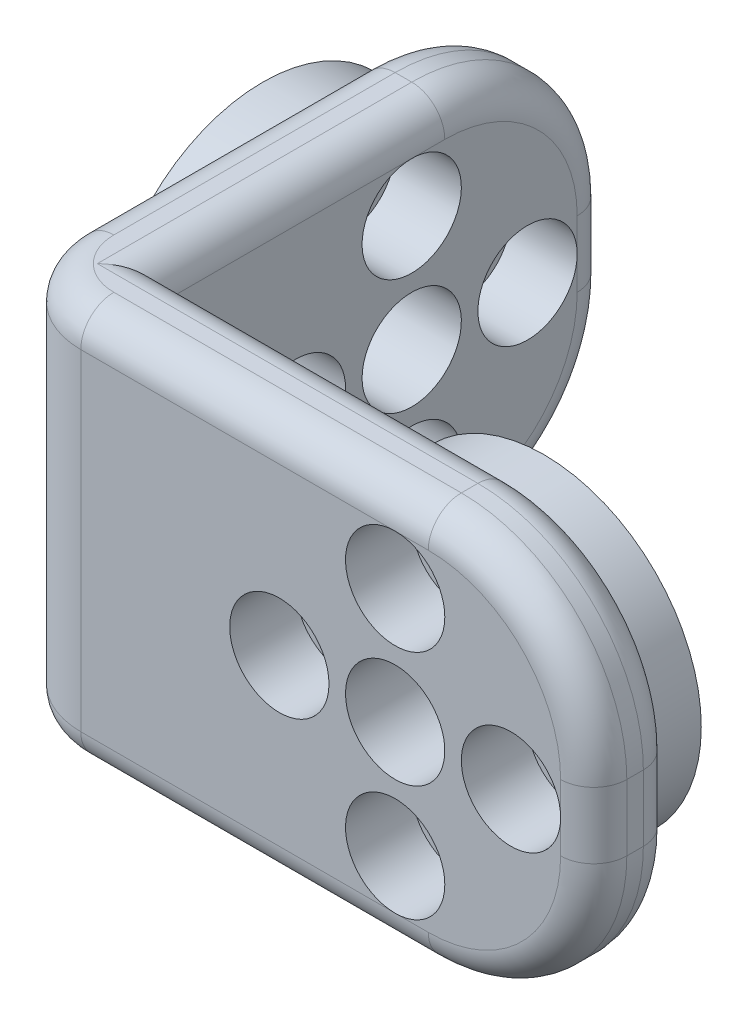
SolidWorks part; units mm, degrees
ref_plane "前视基准面" through (0, 0, 0) normal (0, 0, 1) x (1, 0, 0)
ref_plane "上视基准面" through (0, 0, 0) normal (0, 1, 0) x (1, 0, 0)
ref_plane "右视基准面" through (0, 0, 0) normal (1, 0, 0) x (0, 0, -1)
sketch "草图1" plane through (0, 0, 0) normal (0, 0, 1) x (1, 0, 0)
  line L1 (-12.7013, -5.974) -> (21.2987, -5.974)
  line L2 (-12.7013, -5.974) -> (-12.7013, 14.026)
  line L3 (-12.7013, 14.026) -> (21.2987, 14.026)
  line L4 (21.2987, -5.974) -> (21.2987, 14.026)
  dimension "D1" = 34
  dimension "D2" = 20
extrude "凸台-拉伸1" add sketch "草图1" along normal blind 30
sketch "草图2" plane through (0, 0, 0) normal (0, 0, -1) x (-1, 0, 0)
  line L0 (-21.2987, -5.974) -> (-21.2987, 14.026) construction
  line L1 (-21.2987, 14.026) -> (7.7013, 14.026)
  line L2 (-21.2987, 14.026) -> (-21.2987, -5.974)
  line L3 (-21.2987, -5.974) -> (7.7013, -5.974)
  line L4 (7.7013, 14.026) -> (7.7013, -5.974)
  line L5 (-21.2987, 14.026) -> (12.7013, 14.026) construction
  line L6 (12.7013, -5.974) -> (-21.2987, -5.974) construction
  dimension "D1" = 0
  dimension "D2" = 0
  dimension "D3" = 0
  dimension "D4" = 29
extrude "切除-拉伸1" cut sketch "草图2" against normal blind 25
sketch "草图7" plane through (-12.7013, 0, 0) normal (-1, 0, 0) x (0, 0, 1)
  line L0 (0, 14.026) -> (0, -5.974) construction
  line L1 (30, 14.026) -> (0, 14.026) construction
  circle A0 centre (10, 4.026) radius 9.5
  dimension "D1" = 10
  dimension "D3" = 19
  dimension "D2" = 10
extrude "凸台-拉伸3" add sketch "草图7" along normal blind 4
sketch "草图4" plane through (-12.7013, 0, 0) normal (-1, 0, 0) x (0, 0, 1)
  line L0 (30, 14.026) -> (0, 14.026) construction
  line L1 (0, 14.026) -> (0, -5.974) construction
  circle A0 centre (10, 4.026) radius 10
  circle A1 centre (10, 11.026) radius 1.5
  circle A2 centre (3, 4.026) radius 1.5
  circle A3 centre (10, -2.974) radius 1.5
  circle A4 centre (17, 4.026) radius 1.5
  dimension "D1" = 20
  dimension "D4" = 3
  dimension "D5" = 3
  dimension "D6" = 3
  dimension "D7" = 3
  dimension "D8" = 14
  dimension "D9" = 14
  dimension "D10" = 7
  dimension "D11" = 7
  dimension "D12" = 10
  dimension "D13" = 10
  dimension "D14" = 10
  dimension "D15" = 10
  dimension "D2" = 10
  dimension "D3" = 10
extrude "切除-拉伸5" cut sketch "草图4" against normal mid plane 10 contours A2 | A1 | A4 | A3
sketch "草图6" plane through (0, 0, 25) normal (0, 0, -1) x (-1, 0, 0)
  line L0 (-21.2987, 14.026) -> (-21.2987, -5.974) construction
  line L1 (-21.2987, -5.974) -> (7.7013, -5.974) construction
  circle A0 centre (-11.2987, 4.026) radius 9.5
  dimension "D1" = 10
  dimension "D3" = 19
  dimension "D2" = 10
extrude "凸台-拉伸2" add sketch "草图6" along normal blind 4
sketch "草图5" plane through (0, 0, 30) normal (0, 0, 1) x (1, 0, 0)
  line L0 (21.2987, 14.026) -> (-12.7013, 14.026) construction
  line L1 (21.2987, -5.974) -> (21.2987, 14.026) construction
  line L2 (-12.7013, -5.974) -> (21.2987, -5.974) construction
  circle A0 centre (11.2987, 4.026) radius 10
  circle A1 centre (11.2987, 11.026) radius 1.5
  circle A2 centre (11.2987, -2.974) radius 1.5
  circle A3 centre (4.2987, 4.026) radius 1.5
  circle A4 centre (18.2987, 4.026) radius 1.5
  dimension "D3" = 20
  dimension "D4" = 3
  dimension "D5" = 3
  dimension "D6" = 3
  dimension "D7" = 3
  dimension "D8" = 14
  dimension "D9" = 14
  dimension "D10" = 7
  dimension "D11" = 7
  dimension "D12" = 10
  dimension "D13" = 10
  dimension "D14" = 10
  dimension "D15" = 10
  dimension "D1" = 10
  dimension "D2" = 10
extrude "切除-拉伸6" cut sketch "草图5" against normal blind 10 contours A4 | A2 | A3 | A1
sketch "草图9" plane through (0, 0, 21) normal (0, 0, -1) x (-1, 0, 0)
  circle A0 centre (-11.2987, 4.026) radius 3
  circle A1 centre (-11.2987, 4.026) radius 9.5 construction
  dimension "D2" = 6
  dimension "D1" = 0
extrude "切除-拉伸7" cut sketch "草图9" against normal blind 10
sketch "草图10" plane through (-16.7013, 0, 0) normal (-1, 0, 0) x (0, 0, 1)
  circle A0 centre (10, 4.026) radius 3
  circle A1 centre (10, 4.026) radius 9.5 construction
  dimension "D1" = 0
  dimension "D2" = 6
extrude "切除-拉伸8" cut sketch "草图10" against normal blind 10
sketch "草图12" plane through (0, 14.026, 0) normal (0, 1, 0) x (1, 0, 0)
  line L6 (21.2987, -25) -> (-7.7013, -25)
  line L7 (-7.7013, -25) -> (-7.7013, 0)
  line L8 (-7.7013, 0) -> (-12.7013, 0)
  line L9 (-12.7013, 0) -> (-12.7013, -30)
  line L10 (-12.7013, -30) -> (21.2987, -30)
  line L11 (21.2987, -30) -> (21.2987, -25)
  line L12 (21.2987, -25) -> (-7.7013, -25)
  line L13 (-7.7013, -25) -> (-7.7013, 0)
  line L14 (-7.7013, 0) -> (-12.7013, 0)
  line L15 (-12.7013, 0) -> (-12.7013, -30)
  line L16 (-12.7013, -30) -> (21.2987, -30)
  line L17 (21.2987, -30) -> (21.2987, -25)
  dimension "D1" = 0
extrude "凸台-拉伸4" add sketch "草图12" along normal blind 2
sketch "草图13" plane through (0, -5.974, 0) normal (0, -1, 0) x (1, 0, 0)
  line L6 (-7.7013, 25) -> (21.2987, 25)
  line L7 (21.2987, 25) -> (21.2987, 30)
  line L8 (21.2987, 30) -> (-12.7013, 30)
  line L9 (-12.7013, 30) -> (-12.7013, 0)
  line L10 (-12.7013, 0) -> (-7.7013, 0)
  line L11 (-7.7013, 0) -> (-7.7013, 25)
  line L12 (-7.7013, 25) -> (21.2987, 25)
  line L13 (21.2987, 25) -> (21.2987, 30)
  line L14 (21.2987, 30) -> (-12.7013, 30)
  line L15 (-12.7013, 30) -> (-12.7013, 0)
  line L16 (-12.7013, 0) -> (-7.7013, 0)
  line L17 (-7.7013, 0) -> (-7.7013, 25)
  dimension "D1" = 0
extrude "凸台-拉伸5" add sketch "草图13" along normal blind 2
sketch "草图14" plane through (21.2987, 0, 0) normal (1, 0, 0) x (0, 0, -1)
  line L4 (-25, -7.974) -> (-25, 16.026)
  line L5 (-25, 16.026) -> (-30, 16.026)
  line L6 (-30, 16.026) -> (-30, -7.974)
  line L7 (-30, -7.974) -> (-25, -7.974)
  line L8 (-25, -7.974) -> (-25, 16.026)
  line L9 (-25, 16.026) -> (-30, 16.026)
  line L10 (-30, 16.026) -> (-30, -7.974)
  line L11 (-30, -7.974) -> (-25, -7.974)
  dimension "D1" = 0
extrude "凸台-拉伸6" add sketch "草图14" along normal blind 2
sketch "草图15" plane through (0, 0, 0) normal (0, 0, -1) x (-1, 0, 0)
  line L4 (7.7013, 16.026) -> (7.7013, -7.974)
  line L5 (7.7013, -7.974) -> (12.7013, -7.974)
  line L6 (12.7013, -7.974) -> (12.7013, 16.026)
  line L7 (12.7013, 16.026) -> (7.7013, 16.026)
  line L8 (7.7013, 16.026) -> (7.7013, -7.974)
  line L9 (7.7013, -7.974) -> (12.7013, -7.974)
  line L10 (12.7013, -7.974) -> (12.7013, 16.026)
  line L11 (12.7013, 16.026) -> (7.7013, 16.026)
  dimension "D1" = 0
extrude "凸台-拉伸7" add sketch "草图15" along normal blind 2
sketch "草图16" plane through (0, 0, 30) normal (0, 0, 1) x (1, 0, 0)
  circle A0 centre (11.2987, 11.026) radius 3
  circle A1 centre (4.2987, 4.026) radius 3
  circle A2 centre (11.2987, -2.974) radius 3
  circle A3 centre (18.2987, 4.026) radius 3
  dimension "D1" = 6
  dimension "D2" = 6
  dimension "D3" = 6
  dimension "D4" = 6
extrude "切除-拉伸10" cut sketch "草图16" against normal blind 4
sketch "草图17" plane through (-7.7013, 0, 0) normal (1, 0, 0) x (0, 0, -1)
  circle A0 centre (-10, 11.026) radius 3
  circle A1 centre (-17, 4.026) radius 3
  circle A2 centre (-10, -2.974) radius 3
  circle A3 centre (-3, 4.026) radius 3
  dimension "D1" = 6
  dimension "D2" = 6
  dimension "D3" = 6
  dimension "D4" = 6
extrude "切除-拉伸11" cut sketch "草图17" against normal blind 4
fillet "圆角5" radius 10 1 edges at (-10.2013, 16.026, -2)
fillet "圆角6" radius 10 1 edges at (-10.2013, -7.974, -2)
fillet "圆角9" radius 10 1 edges at (23.2987, -7.974, 27.5)
fillet "圆角10" radius 10 1 edges at (23.2987, 16.026, 27.5)
fillet "圆角11" radius 5 1 edges at (-12.7013, 4.026, 30)
fillet "圆角12" radius 2 12 edges at (-11.2368, 16.026, 28.5355) (-12.7013, 16.026, 16.5) (-12.7013, 13.097, 0.9289) (-12.7013, 4.026, -2) (-12.7013, -5.0451, 0.9289) (-12.7013, -7.974, 16.5) (-11.2368, -7.974, 28.5355) (2.7987, -7.974, 30) (20.3698, -5.0451, 30) (23.2987, 4.026, 30) (20.3698, 13.097, 30) (2.7987, 16.026, 30)
fillet "圆角13" radius 2 5 edges at (2.7987, -7.974, 25) (20.3698, -5.0451, 25) (23.2987, 4.026, 25) (20.3698, 13.097, 25) (2.7987, 16.026, 25)
fillet "圆角14" radius 2 5 edges at (-7.7013, 16.026, 17.5) (-7.7013, 13.097, 0.9289) (-7.7013, 4.026, -2) (-7.7013, -5.0451, 0.9289) (-7.7013, -7.974, 17.5)
